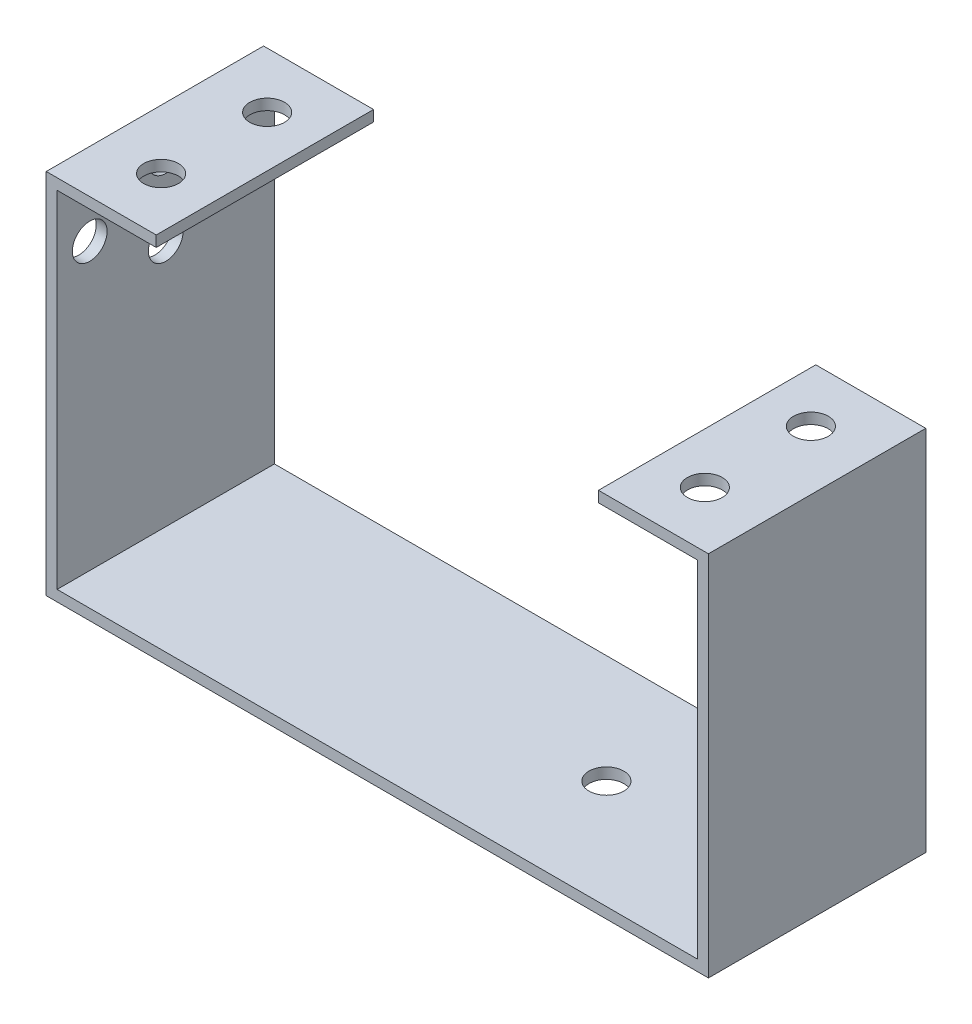
SolidWorks part; units mm, degrees
ref_plane "正面" through (0, 0, 0) normal (0, 0, 1) x (1, 0, 0)
ref_plane "平面" through (0, 0, 0) normal (0, 1, 0) x (1, 0, 0)
ref_plane "右側面" through (0, 0, 0) normal (1, 0, 0) x (0, 0, -1)
sketch "ｽｹｯﾁ2" plane through (0, 0, 0) normal (0, 1, 0) x (1, 0, 0)
  line L1 (0, 0) -> (60.94, 0)
  line L2 (0, 0) -> (0, 20)
  line L3 (0, 20) -> (60.94, 20)
  line L4 (60.94, 0) -> (60.94, 20)
extrude "ﾎﾞｽ - 押し出し1" add sketch "ｽｹｯﾁ2" along normal blind 1
sketch "ｽｹｯﾁ3" plane through (0, 1, 0) normal (0, 1, 0) x (1, 0, 0)
  line L0 (0, 0) -> (60.94, 0) construction
  line L1 (60.94, 20) -> (59.94, 20)
  line L2 (60.94, 20) -> (60.94, 0)
  line L3 (60.94, 0) -> (59.94, 0)
  line L4 (59.94, 20) -> (59.94, 0)
extrude "ﾎﾞｽ - 押し出し2" add sketch "ｽｹｯﾁ3" along normal blind 32.81
sketch "ｽｹｯﾁ4" plane through (0, 1, 0) normal (0, 1, 0) x (1, 0, 0)
  line L0 (0, 0) -> (59.94, 0) construction
  line L1 (0, 20) -> (1, 20)
  line L2 (0, 20) -> (0, 0)
  line L3 (0, 0) -> (1, 0)
  line L4 (1, 20) -> (1, 0)
extrude "ﾎﾞｽ - 押し出し3" add sketch "ｽｹｯﾁ4" along normal blind 32.81
sketch "ｽｹｯﾁ9" plane through (59.94, 0, 0) normal (-1, 0, 0) x (0, 0, 1)
  line L0 (0, 33.81) -> (0, 1) construction
  line L1 (-20, 33.81) -> (0, 33.81)
  line L2 (-20, 33.81) -> (-20, 32.81)
  line L3 (-20, 32.81) -> (0, 32.81)
  line L4 (0, 33.81) -> (0, 32.81)
extrude "ﾎﾞｽ - 押し出し8" add sketch "ｽｹｯﾁ9" along normal blind 9.12
sketch "ｽｹｯﾁ10" plane through (1, 0, 0) normal (1, 0, 0) x (0, 0, -1)
  line L0 (20, 33.81) -> (20, 1) construction
  line L1 (0, 33.81) -> (20, 33.81)
  line L2 (0, 33.81) -> (0, 32.81)
  line L3 (0, 32.81) -> (20, 32.81)
  line L4 (20, 33.81) -> (20, 32.81)
extrude "ﾎﾞｽ - 押し出し9" add sketch "ｽｹｯﾁ10" along normal blind 9.12
sketch "ｽｹｯﾁ13" plane through (0, 33.81, 0) normal (0, 1, 0) x (1, 0, 0)
  circle A0 centre (55.49, 5.12) radius 1.6
extrude "ｶｯﾄ - 押し出し2" cut sketch "ｽｹｯﾁ13" against normal blind 1
sketch "ｽｹｯﾁ14" plane through (0, 33.81, 0) normal (0, 1, 0) x (1, 0, 0)
  circle A0 centre (55.49, 14.88) radius 1.6
extrude "ｶｯﾄ - 押し出し3" cut sketch "ｽｹｯﾁ14" against normal blind 1
sketch "ｽｹｯﾁ15" plane through (0, 33.81, 0) normal (0, 1, 0) x (1, 0, 0)
  circle A0 centre (5.45, 5.12) radius 1.6
extrude "ｶｯﾄ - 押し出し4" cut sketch "ｽｹｯﾁ15" against normal blind 1
sketch "ｽｹｯﾁ16" plane through (0, 33.81, 0) normal (0, 1, 0) x (1, 0, 0)
  circle A0 centre (5.45, 14.88) radius 1.6
extrude "ｶｯﾄ - 押し出し5" cut sketch "ｽｹｯﾁ16" against normal blind 1
sketch "ｽｹｯﾁ17" plane through (0, 0, 0) normal (0, -1, 0) x (-1, 0, 0)
  circle A0 centre (-41.55, 10) radius 1.6
extrude "ｶｯﾄ - 押し出し6" cut sketch "ｽｹｯﾁ17" against normal blind 1 contours A0
sketch "ｽｹｯﾁ19" plane through (0, 0, 0) normal (-1, 0, 0) x (0, 0, 1)
  circle A0 centre (-3, 27.25) radius 1.6
extrude "ｶｯﾄ - 押し出し7" cut sketch "ｽｹｯﾁ19" against normal blind 1
sketch "ｽｹｯﾁ20" plane through (0, 0, 0) normal (-1, 0, 0) x (0, 0, 1)
  circle A0 centre (-17, 27.25) radius 1.6
extrude "ｶｯﾄ - 押し出し8" cut sketch "ｽｹｯﾁ20" against normal blind 1
sketch "ｽｹｯﾁ22" plane through (0, 0, 0) normal (-1, 0, 0) x (0, 0, 1)
  circle A0 centre (-10, 23.75) radius 1.6
extrude "ｶｯﾄ - 押し出し9" cut sketch "ｽｹｯﾁ22" against normal blind 1
sketch "ｽｹｯﾁ23" plane through (0, 0, 0) normal (-1, 0, 0) x (0, 0, 1)
  circle A0 centre (-10, 30.75) radius 1.6
extrude "ｶｯﾄ - 押し出し10" cut sketch "ｽｹｯﾁ23" against normal blind 1
